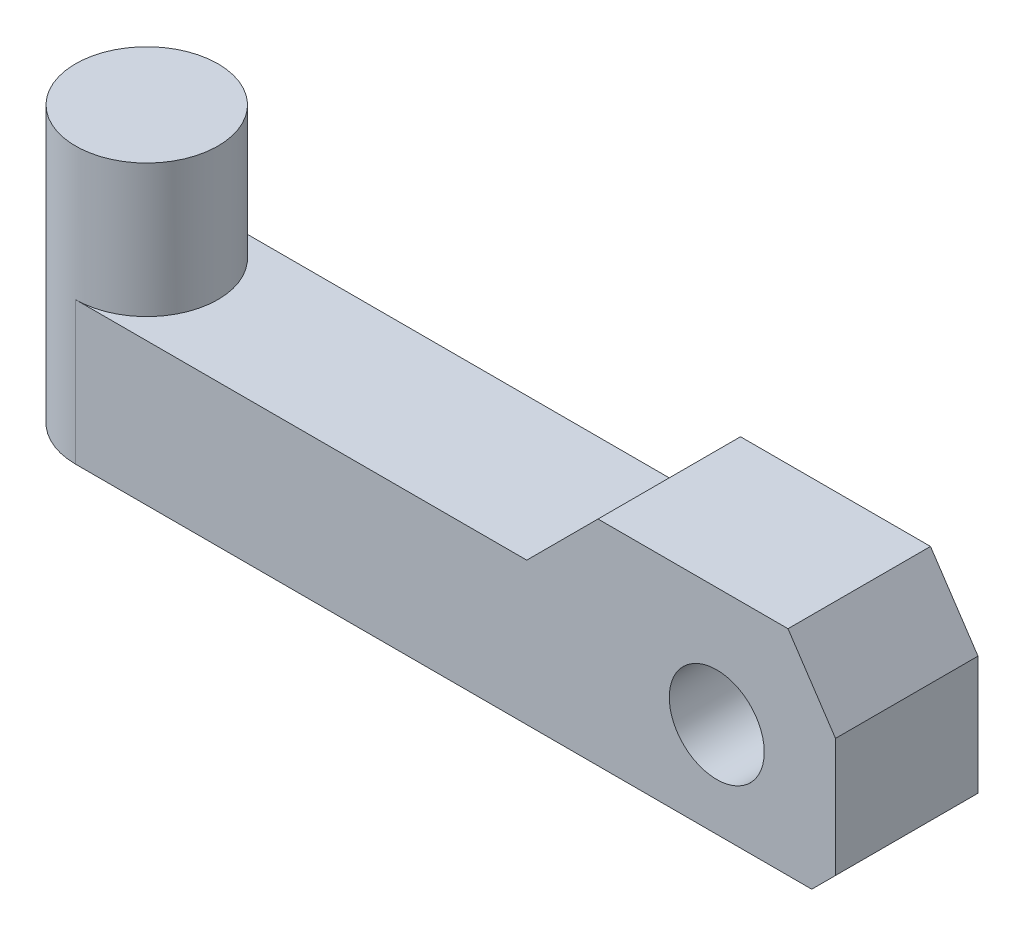
SolidWorks part; units mm, degrees
ref_plane "Front Plane" through (0, 0, 0) normal (0, 0, 1) x (1, 0, 0)
ref_plane "Top Plane" through (0, 0, 0) normal (0, 1, 0) x (1, 0, 0)
ref_plane "Right Plane" through (0, 0, 0) normal (1, 0, 0) x (0, 0, -1)
sketch "Sketch1" plane through (0, 0, 0) normal (0, 1, 0) x (1, 0, 0)
  line L1 (-8, -1.5) -> (8, -1.5)
  line L2 (-8, -1.5) -> (-8, 1.5)
  line L3 (-8, 1.5) -> (8, 1.5)
  line L4 (8, -1.5) -> (8, 1.5)
  line L5 (-8, -1.5) -> (8, 1.5) construction
  line L6 (-8, 1.5) -> (8, -1.5) construction
  point P0 (0, 0)
  dimension "D1" = 16
  dimension "D2" = 3
extrude "Boss-Extrude1" add sketch "Sketch1" along normal blind 3
sketch "Sketch2" plane through (0, 3, 0) normal (0, 1, 0) x (1, 0, 0)
  line L0 (-8, -1.5) -> (8, -1.5) construction
  line L1 (7, 1.5) -> (3, 1.5)
  line L2 (7, 1.5) -> (7, -1.5)
  line L3 (7, -1.5) -> (3, -1.5)
  line L4 (3, 1.5) -> (3, -1.5)
  line L5 (8, -1.5) -> (8, 1.5) construction
  dimension "D1" = 5
  dimension "D2" = 1
extrude "Boss-Extrude2" add sketch "Sketch2" along normal blind 1.5
sketch "Sketch6" plane through (0, 0, 1.5) normal (0, 0, 1) x (1, 0, 0)
  line L0 (3, 4.5) -> (1.5, 3)
  line L1 (-8, 3) -> (3, 3) construction
  line L2 (1.5, 3) -> (3, 3)
  line L3 (3, 3) -> (3, 4.5)
  line L4 (7, 4.5) -> (7, 3)
  line L5 (7, 3) -> (8, 3)
  line L6 (8, 3) -> (7, 4.5)
  dimension "D1" = 1.5
extrude "Boss-Extrude4" add sketch "Sketch6" against normal up to surface (3 mm away) up to face at (2.5, 2.625, -1.5)
hole_wizard "Ø2.0 (2) Diameter Hole1" positions "Sketch3" profile "Sketch4" hole size "Ø2.0" standard "DIN" end condition through all
sketch "Sketch3" plane through (0, 0, 1.5) normal (0, 0, 1) x (1, 0, 0)
  line L0 (-8, 0) -> (8, 0) construction
  line L1 (8, 3) -> (8, 0) construction
  point P0 (5.5, 2)
  dimension "D1" = 2
  dimension "D2" = 2.5
sketch "Sketch4" plane through (5.5, 2, 1.5) normal (1, 0, 0) x (0, -1, 0)
  line L0 (0, 0) -> (0, 3)
  line L1 (0, 3) -> (1, 3)
  line L2 (1, 3) -> (1, 0)
  line L5 (1, 0) -> (0, 0)
  line L11 (0, -6.35) -> (0, 107.95) construction
  dimension "Thru Hole Dia." = 2
  dimension "Thru Hole Depth" = 3
sketch "Sketch7" plane through (0, 0, 0) normal (0, -1, 0) x (1, 0, 0)
  line L0 (-8, -1.5) -> (-8, 1.5) construction
  circle A0 centre (-8, 0) radius 1.5
extrude "Boss-Extrude5" add sketch "Sketch7" against normal blind 5.8
sketch "Sketch8" plane through (0, 0, 1.5) normal (0, 0, 1) x (1, 0, 0)
  line L0 (8, 0) -> (7.5, 0)
  line L1 (-8, 0) -> (8, 0) construction
  line L2 (7.5, 0) -> (8, 0.5)
  line L3 (8, 3) -> (8, 0) construction
  line L4 (8, 0.5) -> (8, 0)
  dimension "D1" = 0.5
  dimension "D2" = 0.5
extrude "Cut-Extrude1" cut sketch "Sketch8" against normal up to surface (3 mm away) up to face at (6.5, 2, -1.5)
